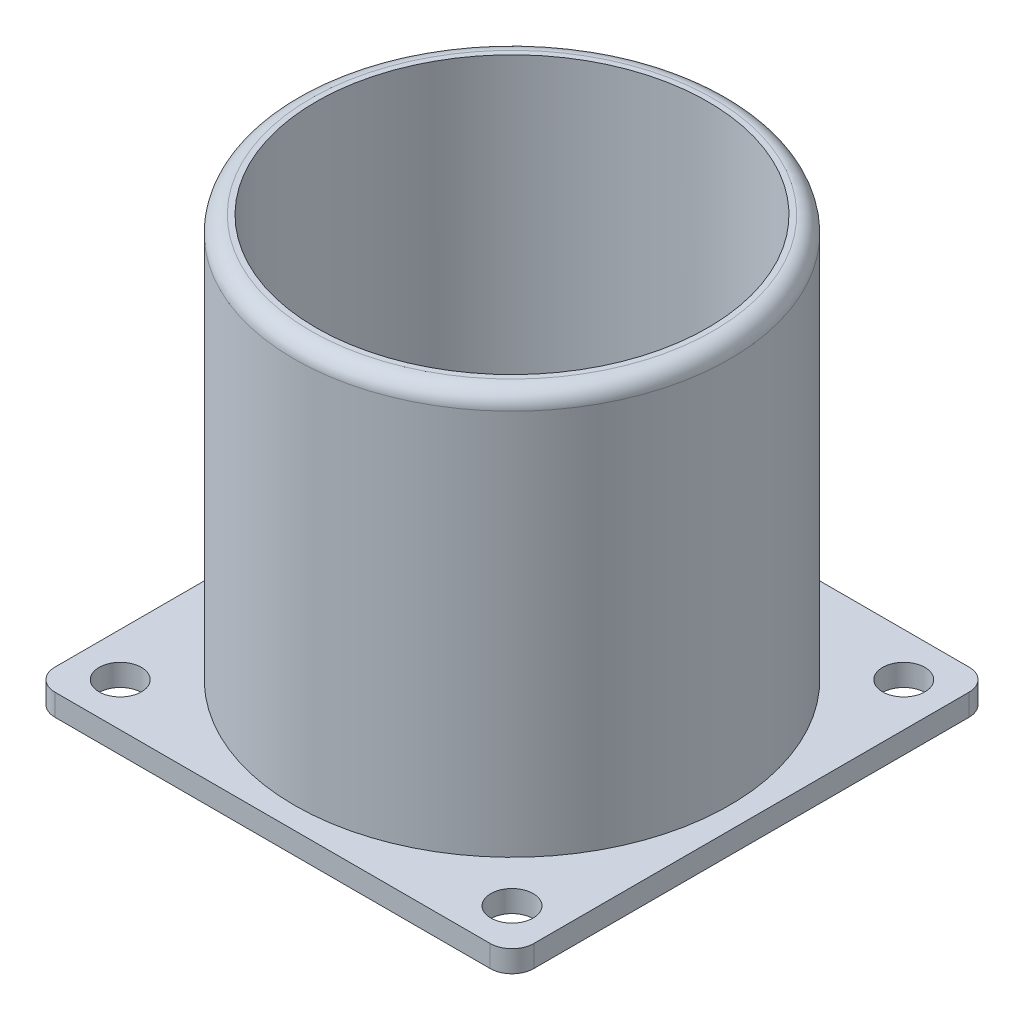
SolidWorks part; units mm, degrees
ref_plane "Plano frontal" through (0, 0, 0) normal (0, 0, 1) x (1, 0, 0)
ref_plane "Plano superior" through (0, 0, 0) normal (0, 1, 0) x (1, 0, 0)
ref_plane "Plano direito" through (0, 0, 0) normal (1, 0, 0) x (0, 0, -1)
sketch "Esboço1" plane through (0, 0, 0) normal (0, 1, 0) x (1, 0, 0)
  line L0 (0, 0) -> (0, 18) construction
  line L1 (-22, -22) -> (22, -22)
  line L2 (-22, -22) -> (-22, 22)
  line L3 (-22, 22) -> (22, 22)
  line L4 (22, -22) -> (22, 22)
  line L5 (-22, -22) -> (22, 22) construction
  line L6 (-22, 22) -> (22, -22) construction
  line L7 (-22, -18) -> (-18, -18) construction
  line L8 (-22, -18) -> (-22, -22) construction
  line L9 (-22, -22) -> (-18, -22) construction
  line L10 (-18, -18) -> (-18, -22) construction
  line L11 (-22, -18) -> (-18, -22) construction
  line L12 (-22, -22) -> (-18, -18) construction
  line L13 (0, 0) -> (8.3253, 0) construction
  line L14 (0.75, -17.9844) -> (0.75, 18)
  line L15 (-18, -18) -> (-16.05, -18) construction
  line L16 (-18, -18) -> (-18, -16.05) construction
  line L17 (-18, 18) -> (-6.75, 18) construction
  line L18 (18, -18) -> (18, 18) construction
  line L19 (-18, -18) -> (18, 18) construction
  line L20 (-18, 18) -> (18, -18) construction
  line L21 (-0.75, -17.9844) -> (-0.75, 18)
  line L22 (-0.75, 0) -> (-0.75, 22) construction
  line L23 (0.75, 0) -> (0.75, 22) construction
  line L24 (0.75, 18) -> (0.75, 22) construction
  line L25 (0, 17.7309) -> (0, 22) construction
  line L26 (0, 0) -> (0, 22) construction
  line L27 (-0.75, 18) -> (-0.75, 22) construction
  line L28 (0.75, -17.9844) -> (0.75, 18)
  line L29 (2.25, -17.9844) -> (2.25, 18)
  line L30 (2.25, -17.9844) -> (2.25, 18)
  line L31 (3.75, -17.9844) -> (3.75, 18)
  line L32 (3.75, -17.9844) -> (3.75, 18)
  line L33 (5.25, -17.9844) -> (5.25, 18)
  line L34 (5.25, -17.9844) -> (5.25, 18)
  line L35 (6.75, -17.9844) -> (6.75, 18)
  line L36 (6.75, -17.9844) -> (6.75, 18)
  line L37 (8.25, -17.9844) -> (8.25, 18)
  line L38 (8.25, -17.9844) -> (8.25, 18)
  line L39 (9.75, -17.9844) -> (9.75, 18)
  line L40 (9.75, -17.9844) -> (9.75, 18)
  line L41 (11.25, -17.9844) -> (11.25, 18)
  line L42 (11.25, -17.9844) -> (11.25, 18)
  line L43 (12.75, -17.9844) -> (12.75, 18)
  line L44 (12.75, -17.9844) -> (12.75, 18)
  line L45 (14.25, -17.9844) -> (14.25, 18)
  line L46 (14.25, -17.9844) -> (14.25, 18)
  line L47 (15.75, -17.9844) -> (15.75, 18)
  line L48 (15.75, -17.9844) -> (15.75, 18)
  line L49 (17.25, -17.9844) -> (17.25, 18)
  line L50 (-0.75, -17.9844) -> (0.75, -17.9844) construction
  line L51 (-0.75, 18) -> (0, 18) construction
  line L52 (0.75, 18) -> (2.25, 18) construction
  line L53 (0, 18) -> (0.75, 18) construction
  line L54 (-16.05, -18) -> (0, -18) construction
  line L55 (16.05, -18) -> (18, -18) construction
  line L56 (0, -18) -> (16.05, -18) construction
  line L57 (2.25, 18) -> (3.75, 18) construction
  line L58 (3.75, 18) -> (5.25, 18) construction
  line L59 (5.25, 18) -> (6.75, 18) construction
  line L60 (6.75, 18) -> (18, 18) construction
  line L61 (-17.25, -17.9844) -> (-17.25, 18)
  line L62 (-15.75, -17.9844) -> (-15.75, 18)
  line L63 (-14.25, -17.9844) -> (-14.25, 18)
  line L64 (-12.75, -17.9844) -> (-12.75, 18)
  line L65 (-11.25, -17.9844) -> (-11.25, 18)
  line L66 (-9.75, -17.9844) -> (-9.75, 18)
  line L67 (-8.25, -17.9844) -> (-8.25, 18)
  line L68 (-6.75, -17.9844) -> (-6.75, 18)
  line L69 (-5.25, -17.9844) -> (-5.25, 18)
  line L70 (-3.75, -17.9844) -> (-3.75, 18)
  line L71 (-2.25, -17.9844) -> (-2.25, 18)
  line L72 (-3.75, 18) -> (-2.25, 18) construction
  line L73 (-2.25, 18) -> (-0.75, 18) construction
  line L74 (-6.75, 18) -> (-5.25, 18) construction
  line L75 (-5.25, 18) -> (-3.75, 18) construction
  line L76 (-18, 0) -> (-18, 16.05) construction
  line L77 (-18, 16.05) -> (-18, 18) construction
  line L78 (-18, -16.05) -> (-18, 0) construction
  arc A0 (-0.75, 17.9844) -> (-2.25, 17.8588) centre (0, 0) ccw
  circle A1 centre (-18, -18) radius 1.95
  circle A2 centre (18, -18) radius 1.95
  circle A3 centre (18, 18) radius 1.95
  circle A4 centre (-18, 18) radius 1.95
  arc A5 (0, 18) -> (-0.75, 17.9844) centre (0, 0) ccw construction
  arc A6 (0.75, 17.9844) -> (0, 18) centre (0, 0) ccw construction
  arc A7 (-0.75, -17.9844) -> (0, -18) centre (0, 0) ccw construction
  arc A8 (0, -18) -> (2.25, -17.8588) centre (0, 0) ccw
  arc A9 (2.25, -17.8588) -> (3.75, -17.605) centre (0, 0) ccw construction
  arc A10 (3.75, -17.605) -> (5.25, -17.2174) centre (0, 0) ccw
  arc A11 (3.75, 17.605) -> (2.25, 17.8588) centre (0, 0) ccw construction
  arc A12 (2.25, 17.8588) -> (0.75, 17.9844) centre (0, 0) ccw
  arc A13 (6.75, 16.6864) -> (5.25, 17.2174) centre (0, 0) ccw construction
  arc A14 (5.25, 17.2174) -> (3.75, 17.605) centre (0, 0) ccw
  arc A15 (5.25, -17.2174) -> (6.75, -16.6864) centre (0, 0) ccw construction
  arc A16 (6.75, -16.6864) -> (8.25, -15.998) centre (0, 0) ccw
  arc A17 (8.25, -15.998) -> (9.75, -15.1307) centre (0, 0) ccw construction
  arc A18 (9.75, -15.1307) -> (11.25, -14.0512) centre (0, 0) ccw
  arc A19 (9.75, 15.1307) -> (8.25, 15.998) centre (0, 0) ccw construction
  arc A20 (8.25, 15.998) -> (6.75, 16.6864) centre (0, 0) ccw
  arc A21 (12.7279, 12.7279) -> (11.25, 14.0512) centre (0, 0) ccw construction
  arc A22 (11.25, 14.0512) -> (9.75, 15.1307) centre (0, 0) ccw
  arc A23 (11.25, -14.0512) -> (12.7279, -12.7279) centre (0, 0) ccw construction
  arc A24 (12.7279, -12.7279) -> (14.25, -10.9972) centre (0, 0) ccw
  arc A25 (14.25, -10.9972) -> (15.75, -8.7142) centre (0, 0) ccw construction
  arc A26 (15.75, -8.7142) -> (17.25, -5.1417) centre (0, 0) ccw
  arc A27 (15.75, 8.7142) -> (14.25, 10.9972) centre (0, 0) ccw construction
  arc A28 (14.25, 10.9972) -> (12.7279, 12.7279) centre (0, 0) ccw
  arc A29 (18, 0) -> (17.25, 5.1417) centre (0, 0) ccw construction
  arc A30 (17.25, 5.1417) -> (15.75, 8.7142) centre (0, 0) ccw
  arc A31 (17.25, -5.1417) -> (18, 0) centre (0, 0) ccw construction
  arc A32 (-2.25, 17.8588) -> (-3.75, 17.605) centre (0, 0) ccw construction
  arc A33 (-3.75, 17.605) -> (-5.25, 17.2174) centre (0, 0) ccw
  arc A34 (-3.75, -17.605) -> (-2.25, -17.8588) centre (0, 0) ccw construction
  arc A35 (-2.25, -17.8588) -> (-0.75, -17.9844) centre (0, 0) ccw
  arc A36 (-6.75, -16.6864) -> (-5.25, -17.2174) centre (0, 0) ccw construction
  arc A37 (-5.25, -17.2174) -> (-3.75, -17.605) centre (0, 0) ccw
  arc A38 (-5.25, 17.2174) -> (-6.75, 16.6864) centre (0, 0) ccw construction
  arc A39 (-6.75, 16.6864) -> (-8.25, 15.998) centre (0, 0) ccw
  arc A40 (-8.25, 15.998) -> (-9.75, 15.1307) centre (0, 0) ccw construction
  arc A41 (-9.75, 15.1307) -> (-11.25, 14.0512) centre (0, 0) ccw
  arc A42 (-9.75, -15.1307) -> (-8.25, -15.998) centre (0, 0) ccw construction
  arc A43 (-8.25, -15.998) -> (-6.75, -16.6864) centre (0, 0) ccw
  arc A44 (-12.7279, -12.7279) -> (-11.25, -14.0512) centre (0, 0) ccw construction
  arc A45 (-11.25, -14.0512) -> (-9.75, -15.1307) centre (0, 0) ccw
  arc A46 (-11.25, 14.0512) -> (-12.7279, 12.7279) centre (0, 0) ccw construction
  arc A47 (-12.7279, 12.7279) -> (-14.25, 10.9972) centre (0, 0) ccw
  arc A48 (-14.25, 10.9972) -> (-15.75, 8.7142) centre (0, 0) ccw construction
  arc A49 (-15.75, 8.7142) -> (-17.25, 5.1417) centre (0, 0) ccw
  arc A50 (-15.75, -8.7142) -> (-14.25, -10.9972) centre (0, 0) ccw construction
  arc A51 (-14.25, -10.9972) -> (-12.7279, -12.7279) centre (0, 0) ccw
  arc A52 (-17.25, 5.1417) -> (-18, 0) centre (0, 0) ccw construction
  arc A53 (-17.25, -5.1417) -> (-15.75, -8.7142) centre (0, 0) ccw
  arc A54 (-18, 0) -> (-17.25, -5.1417) centre (0, 0) ccw construction
  point P7 (-20, -20)
  dimension "D1" = 36
  dimension "D4" = 3.9
  dimension "D2" = 44
  dimension "D3" = 4
  dimension "D8" = 1.5
  dimension "D5" = 0.75
  dimension "D6" = 0.75
  dimension "D7" = 12
extrude "Ressalto-extrusão1" add sketch "Esboço1" along normal blind 2 contours L1 L4 L3 L2 A30 A3 L49 A2 A26 L48 A28 L46 A24 L44 A22 L42 A18 L40 A20 region at (0, 0, 0)
ref_plane "Plano1" through (0, 2, 0) normal (0, 1, 0) x (1, 0, 0)
sketch "Esboço3" plane through (0, 2, 0) normal (0, 1, 0) x (1, 0, 0)
  circle A0 centre (0, 0) radius 18
  arc A1 (5.25, 17.2174) -> (3.75, 17.605) centre (0, 0) ccw construction
  circle A2 centre (0, 0) radius 20
  dimension "D1" = 2
extrude "Ressalto-extrusão3" add sketch "Esboço3" along normal blind 37
fillet "Filete3" radius 1.5 1 edges at (0, 39, 20)
fillet "Filete4" radius 2 4 edges at (-22, 1, -22) (-22, 1, 22) (22, 1, 22) (22, 1, -22)
equation "\"D2@Esboço1\"=\"D1@Esboço1\"+8"
